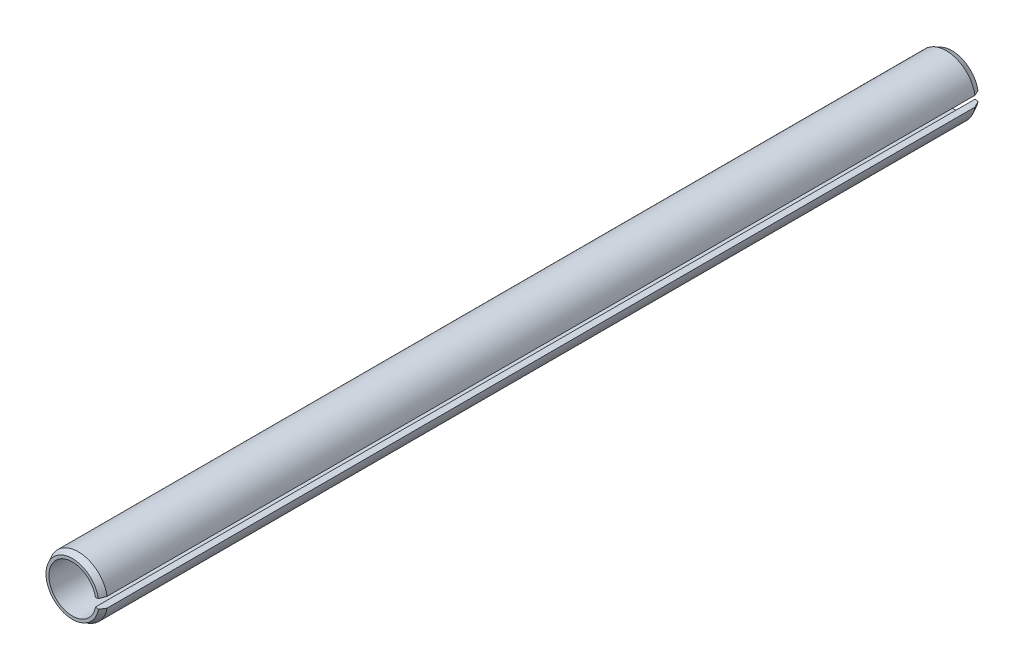
SolidWorks part; units mm, degrees
ref_plane "Front Plane" through (0, 0, 0) normal (0, 0, 1) x (1, 0, 0)
ref_plane "Top Plane" through (0, 0, 0) normal (0, 1, 0) x (1, 0, 0)
ref_plane "Right Plane" through (0, 0, 0) normal (1, 0, 0) x (0, 0, -1)
sketch "Sketch1" plane through (0, 0, 0) normal (0, 1, 0) x (1, 0, 0)
  line L0 (0, 15) -> (0, -15) construction
  line L2 (1, 15) -> (-1, 15) construction
  line L3 (-1, -15) -> (1, -15) construction
  line L4 (-0.9, 15) -> (-1, 14.8) construction
  line L5 (1, 15) -> (1, -15) construction
  line L6 (-1, 15) -> (-1, -15) construction
  line L7 (-0.8, 15) -> (-0.8, -15) construction
  point P3 (-0.8, -15)
  dimension "D1" = 0.1
sketch "Sketch2" plane through (0, 0, 0) normal (0, 1, 0) x (1, 0, 0)
  line L0 (-0.8, 15) -> (-0.9, 15)
  line L1 (-0.9, 15) -> (-1, 14.8)
  line L2 (-1, 14.8) -> (-1, -14.8)
  line L3 (-1, 0) -> (-0.8, 0) construction
  line L4 (-0.8, -15) -> (-0.8, 15)
  line L5 (-0.9, -15) -> (-1, -14.8)
  line L6 (-0.8, -15) -> (-0.9, -15)
revolve "Revolve1" add sketch "Sketch2" angle 340 mid plane about L0
ref_plane "Contact Plane 1" through (0, 0, 15) normal (0, 0, 1) x (1, 0, 0)
ref_plane "Contact Plane 2" through (0, 0, -15) normal (0, 0, -1) x (-1, 0, 0)
ref_axis "Center Axis 1" through (0, 0, 15) along (0, 0, -1)
equation "\"D1@Sketch1\"=\"Wall Thickness@Sketch1\"/2"
